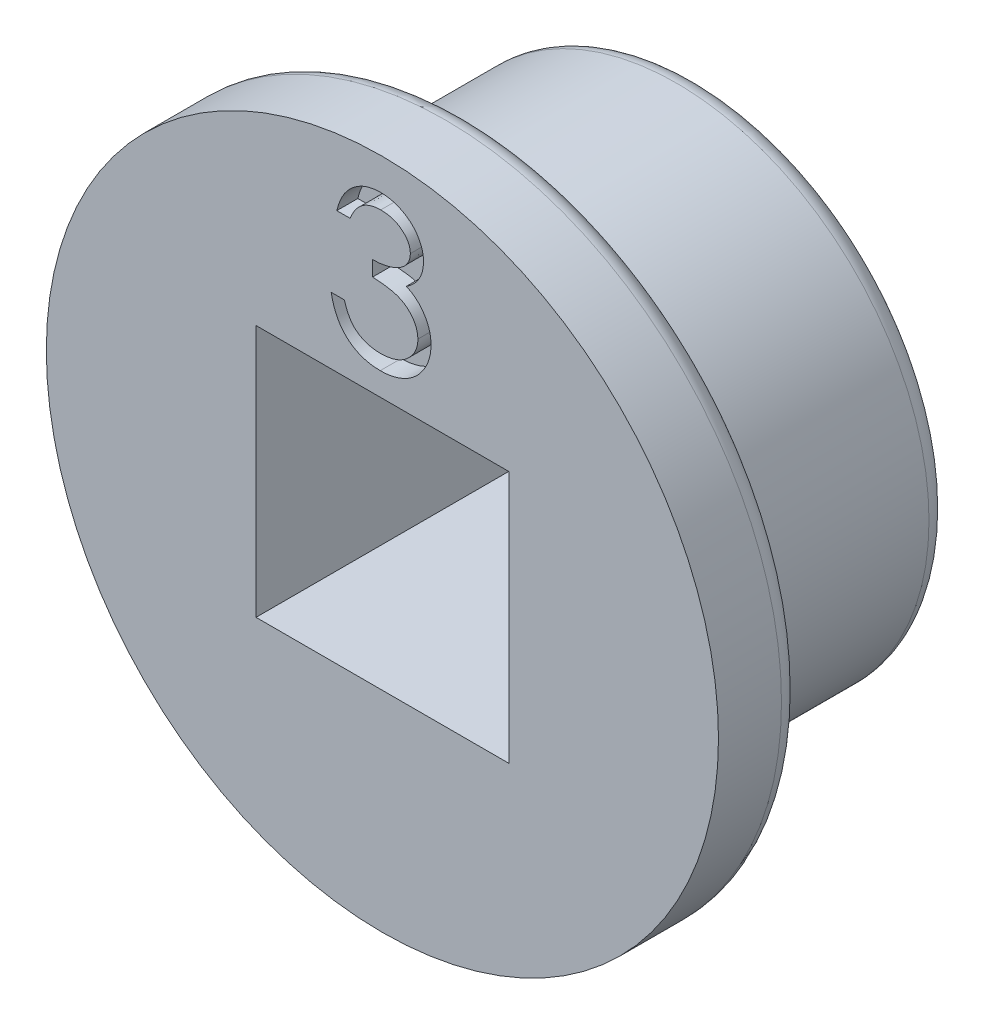
SolidWorks part; units mm, degrees
material "ABS"
ref_plane "Front Plane" through (0, 0, 0) normal (0, 0, 1) x (1, 0, 0)
ref_plane "Top Plane" through (0, 0, 0) normal (0, 1, 0) x (1, 0, 0)
ref_plane "Right Plane" through (0, 0, 0) normal (1, 0, 0) x (0, 0, -1)
sketch "Sketch1" plane through (0, 0, 0) normal (0, 0, 1) x (1, 0, 0)
  line L1 (-3.008, 3.008) -> (3.008, 3.008)
  line L2 (-3.008, 3.008) -> (-3.008, -3.008)
  line L3 (-3.008, -3.008) -> (3.008, -3.008)
  line L4 (3.008, 3.008) -> (3.008, -3.008)
  circle A0 centre (0, 0) radius 6.011
  circle A1 centre (0, 0) radius 8
  point P4 (0, 3.008)
  point P6 (-3.008, 0)
  dimension "D2" = 12.022
  dimension "D3" = 16
  dimension "D1" = 6.016
extrude "Boss-Extrude1" add sketch "Sketch1" against normal blind 5.5 contours A0 L1 L4 L3 L2 region at (-5.841, 0, 0)
extrude "Boss-Extrude2" add sketch "Sketch1<3>" along normal blind 2 contours A1 A0 | A0 L1 L4 L3 L2 region at (-5.841, 0, 0) region at (-7.7737, 0, 0)
sketch "Sketch1<3>" plane through (0, 0, 0) normal (0, 0, 1) x (1, 0, 0) same geometry as "Sketch1"
fillet "Fillet1" radius 0.5 2 edges at (8, 0, 0) (6.011, 0, -5.5)
sketch "Sketch2" plane through (0, 0, 2) normal (0, 0, 1) x (1, 0, 0)
  text T0 "3"
extrude "Cut-Extrude1" cut sketch "Sketch2" against normal blind 0.5
